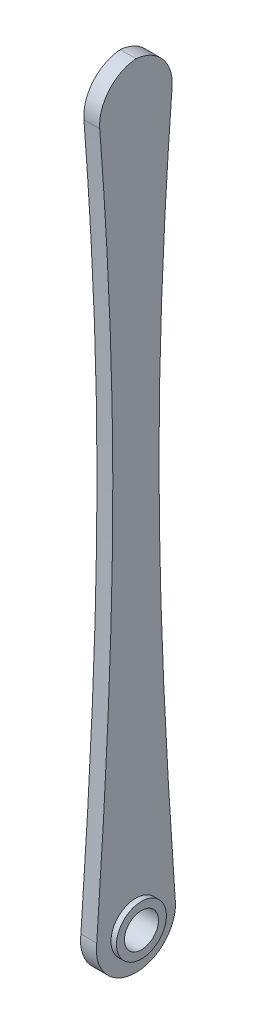
SolidWorks part; units mm, degrees
ref_plane "Front Plane" through (0, 0, 0) normal (0, 0, 1) x (1, 0, 0)
ref_plane "Top Plane" through (0, 0, 0) normal (0, 1, 0) x (1, 0, 0)
ref_plane "Right Plane" through (0, 0, 0) normal (1, 0, 0) x (0, 0, -1)
sketch "Sketch1" plane through (0, 0, 0) normal (0, 1, 0) x (1, 0, 0)
  line L1 (0, 0) -> (2, 0)
  line L2 (0, 0) -> (0, 10)
  line L3 (0, 10) -> (2, 10)
  line L4 (2, 0) -> (2, 10)
  dimension "D1" = 2
  dimension "D2" = 10
extrude "Boss-Extrude1" add sketch "Sketch1" along normal blind 100
sketch "Sketch3" plane through (2, 0, 0) normal (1, 0, 0) x (0, 0, -1)
  line L0 (0, 0) -> (10, 0) construction
  circle A0 centre (5, 5) radius 2.15
  point P2 (2.5901, 1.7475)
  point P5 (5, 0)
  dimension "D1" = 4.3
  dimension "D2" = 5
extrude "Cut-Extrude1" cut sketch "Sketch3" against normal blind 90
fillet "Fillet1" radius 5 2 edges at (1, 0, -10) (1, 0, 0)
sketch "Sketch4" plane through (0, 0, 0) normal (-1, 0, 0) x (0, 0, 1)
  line L0 (-5, 100) -> (-5, 0) construction
  line L1 (-10, 100) -> (0, 100) construction
  line L2 (-10, 100) -> (-10, 5) construction
  line L3 (0, 100) -> (0, 5) construction
  line L4 (-10, 100) -> (-10, 5)
  line L5 (0, 100) -> (0, 5)
  line L6 (-10, 100) -> (0, 100)
  circle A0 centre (-5, 5) radius 5
  spline S0 degree 3 poles (0, 5) (-2.6634, 42.4077) (-2.8861, 65.4643) (0, 100) knots 0 0 0 0 1 1 1 1
  spline S1 degree 3 poles (-10, 5) (-7.3366, 42.4077) (-7.1139, 65.4643) (-10, 100) knots 0 0 0 0 1 1 1 1
  line M4 (-10, 100) -> (-10, 5)
  line M7 (0, 5) -> (0, 100)
extrude "Cut-Extrude2" cut sketch "Sketch4" against normal blind 90 contours A0 S1 M4 | S0 A0 M7
fillet "Fillet2" radius 5 2 edges
sketch "Sketch5" plane through (2, 0, 0) normal (1, 0, 0) x (0, 0, -1)
  circle A0 centre (5, 5) radius 2.15 construction
  circle A1 centre (5, 5) radius 2.15
  circle A2 centre (5, 5) radius 3.15
  dimension "D1" = 1
extrude "Boss-Extrude2" add sketch "Sketch5" along normal blind 0.7
ref_plane "Plane1" through (1, 0, 0) normal (1, 0, 0) x (0, 0, -1)
mirror "Mirror1" about plane through (1, 0, 0) normal (1, 0, 0) of "Boss-Extrude2"
other "Flex1" parameters "D0"=90, "D1"=0, "D2"=0
